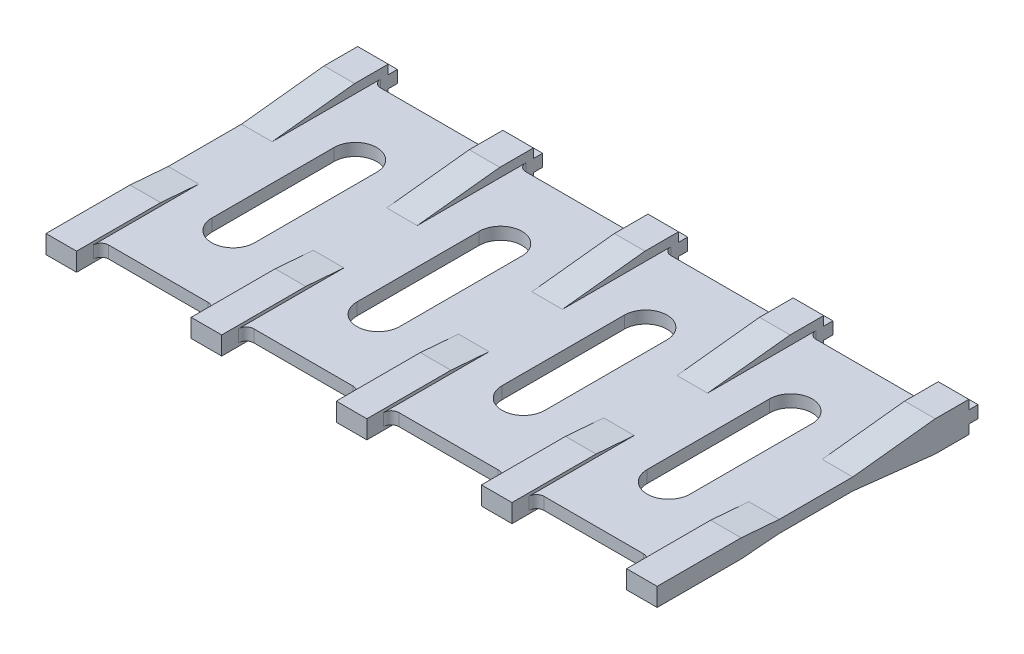
SolidWorks part; units mm, degrees
ref_plane "Спереди" through (0, 0, 0) normal (0, 0, 1) x (1, 0, 0)
ref_plane "Сверху" through (0, 0, 0) normal (0, 1, 0) x (1, 0, 0)
ref_plane "Справа" through (0, 0, 0) normal (1, 0, 0) x (0, 0, -1)
other "Configuration Table"
sketch "Эскиз1" plane through (0, 0, 0) normal (0, 1, 0) x (1, 0, 0)
  line L1 (-100, -52.5) -> (100, -52.5)
  line L2 (-100, -52.5) -> (-100, 52.5)
  line L3 (-100, 52.5) -> (100, 52.5)
  line L4 (100, -52.5) -> (100, 52.5)
  line L5 (-100, -52.5) -> (100, 52.5) construction
  line L6 (-100, 52.5) -> (100, -52.5) construction
  point P0 (0, 0)
  dimension "D1" = 200
  dimension "D2" = 105
extrude "Бобышка-Вытянуть1" add sketch "Эскиз1" along normal blind 4
sketch "Эскиз2" plane through (0, 4, 0) normal (0, 1, 0) x (1, 0, 0)
  line L0 (-100, -52.5) -> (100, -52.5) construction
  line L1 (-90, -52.5) -> (-52.5, -52.5)
  line L2 (-90, -52.5) -> (-90, -47)
  line L3 (-87.5, -44.5) -> (-55, -44.5)
  line L4 (-52.5, -52.5) -> (-52.5, -47)
  line L5 (-100, 52.5) -> (-100, -52.5) construction
  arc A0 (-55, -44.5) -> (-52.5, -47) centre (-55, -47) cw
  arc A1 (-87.5, -44.5) -> (-90, -47) centre (-87.5, -47) ccw
  point P10 (-52.5, -44.5)
  point P13 (-90, -44.5)
  dimension "D4" = 2.5
  dimension "D1" = 10
  dimension "D2" = 37.5
  dimension "D3" = 8
extrude "Вырез-Вытянуть1" cut sketch "Эскиз2" against normal up to surface (4 mm away) up to face at (0, 0, 0)
pattern_linear "Линейный массив1" count 4 spacing 47.5 along (1, 0, 0) of "Вырез-Вытянуть1"
mirror "Зеркальное отражение1" about plane through (0, 0, 0) normal (0, 0, 1) of "Линейный массив1"
sketch "Эскиз3" plane through (0, 0, -52.5) normal (0, 0, -1) x (-1, 0, 0)
  line L0 (100, 4) -> (100, 0) construction
  line L1 (90, 7) -> (100, 7)
  line L2 (90, 7) -> (90, -3)
  line L3 (90, -3) -> (100, -3)
  line L4 (100, 7) -> (100, -3)
  line L5 (90, 7) -> (100, -3) construction
  line L6 (90, -3) -> (100, 7) construction
  line L7 (90, 0) -> (90, 4) construction
  line L8 (90, 4) -> (100, 4) construction
  point P0 (95, 2)
  dimension "D1" = 10
  dimension "D2" = 2
extrude "Бобышка-Вытянуть2" add sketch "Эскиз3" against normal up to surface (52.5 mm away) up to plane "Спереди"
sketch "Эскиз5" plane through (-100, 0, 0) normal (-1, 0, 0) x (0, 0, 1)
  line L0 (-38.5, 7) -> (-11.5, 4)
  line L1 (-52.5, 7) -> (-49.5, 7)
  line L2 (-52.5, 7) -> (-52.5, 4)
  line L3 (-52.5, 4) -> (-49.5, 4)
  line L4 (-49.5, 7) -> (-49.5, 4)
  line L5 (-52.5, -3) -> (-49.5, -3)
  line L6 (-52.5, -3) -> (-52.5, 0)
  line L7 (-52.5, 0) -> (-49.5, 0)
  line L8 (-49.5, -3) -> (-49.5, 0)
  line L9 (0, 7) -> (-52.5, 7) construction
  line L11 (-11.5, 4) -> (0, 4)
  line L14 (-38.5, -3) -> (-11.5, 0)
  line L15 (0, -3) -> (-52.5, -3) construction
  line L16 (50, 0) -> (-50, 0) construction
  line L20 (0, -50) -> (0, 50) construction
  line L33 (0, 0) -> (-11.5, 0)
  line L35 (-38.5, -3) -> (0, -3)
  line L36 (0, -3) -> (0, 0)
  line L37 (0, 4) -> (0, 7)
  line L38 (0, 7) -> (-52.5, 7) construction
  line L39 (0, 4) -> (0, 7) construction
  line L40 (0, 7) -> (-38.5, 7)
  dimension "D1" = 3
  dimension "D2" = 3
  dimension "D3" = 27
  dimension "D4" = 11
  dimension "D10" = 11
extrude "Вырез-Вытянуть2" cut sketch "Эскиз5" against normal up to surface (10 mm away)
pattern_linear "Линейный массив3" count 5 spacing 47.5 along (1, 0, 0) of "Бобышка-Вытянуть2", "Вырез-Вытянуть2"
sketch "Эскиз11" plane through (0, 0, 52.5) normal (0, 0, 1) x (1, 0, 0)
  line L0 (-100, 4) -> (-100, 0) construction
  line L1 (-100, 5) -> (-90, 5)
  line L2 (-100, 5) -> (-100, -1)
  line L3 (-100, -1) -> (-90, -1)
  line L4 (-90, 5) -> (-90, -1)
  line L5 (-100, 5) -> (-90, -1) construction
  line L6 (-100, -1) -> (-90, 5) construction
  line L7 (-100, 4) -> (-90, 4) construction
  point P0 (-95, 2)
  dimension "D1" = 10
  dimension "D2" = 6
  dimension "D3" = 1
extrude "Бобышка-Вытянуть3" add sketch "Эскиз11" against normal up to surface (52.5 mm away) up to plane "Спереди"
chamfer "Фаска1" distance 25 distance2 2 2 edges at (-95, 5, 0) (-95, -1, 0) first distance on face at (-95, 5, 26.25) first distance on face at (-95, -1, 26.25)
pattern_linear "Линейный массив4" count 5 spacing 47.5 along (1, 0, 0) of "Бобышка-Вытянуть3", "Фаска1"
sketch "Эскиз12" plane through (0, 4, 0) normal (0, 1, 0) x (1, 0, 0)
  line L0 (-71.25, 20) -> (-71.25, -20) construction
  line L1 (-64.25, 20) -> (-64.25, -20)
  line L2 (-78.25, 20) -> (-78.25, -20)
  line L3 (-100, 11.5) -> (-100, -12.5) construction
  arc A0 (-64.25, 20) -> (-78.25, 20) centre (-71.25, 20) ccw
  arc A1 (-78.25, -20) -> (-64.25, -20) centre (-71.25, -20) ccw
  point P2 (-71.25, 0)
  point P7 (0, 0)
  dimension "D2" = 40
  dimension "D1" = 14
  dimension "D3" = 28.75
extrude "Вырез-Вытянуть3" cut sketch "Эскиз12" against normal up to surface (4 mm away) up to face at (0, 0, 0.1923)
pattern_linear "Линейный массив5" count 4 spacing 47.5 along (1, 0, 0) of "Вырез-Вытянуть3"
